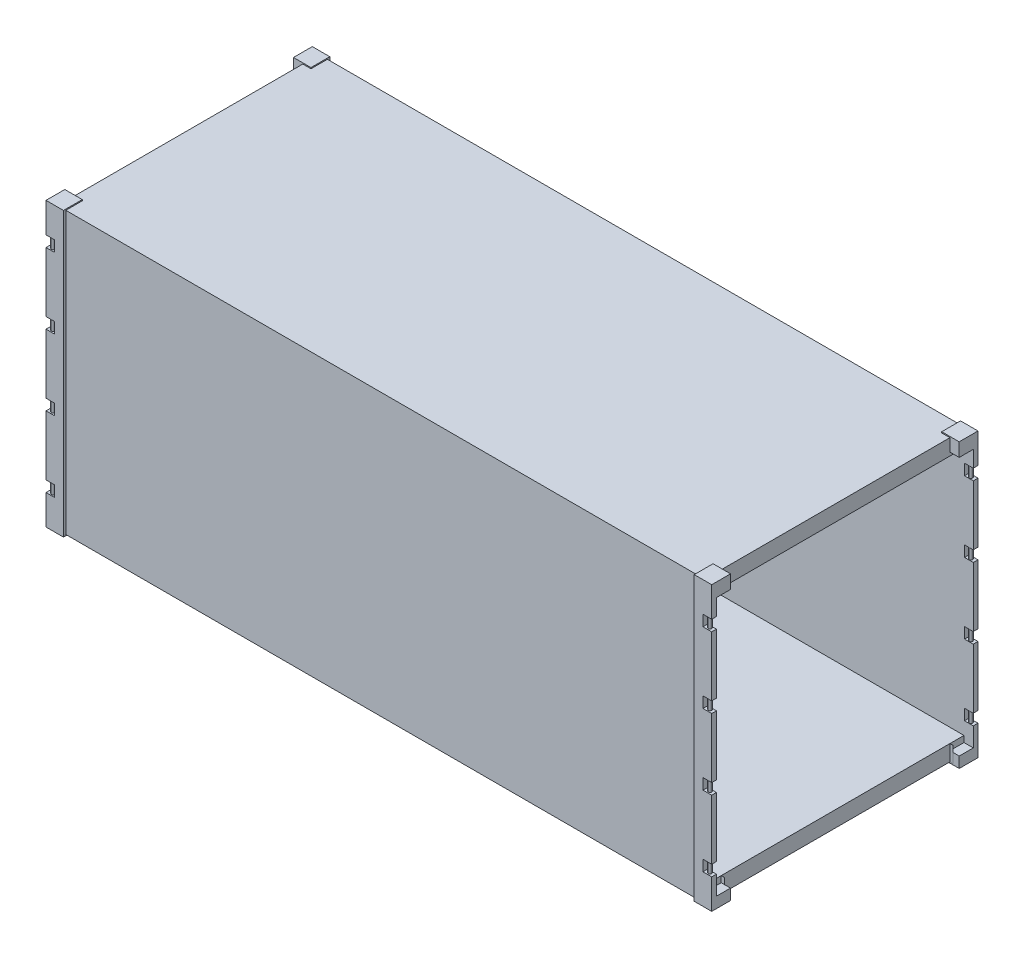
SolidWorks part; units mm, degrees
material "AISI 1015 Steel, Cold Drawn (SS)"
ref_plane "Front Plane" through (0, 0, 0) normal (0, 0, 1) x (1, 0, 0)
ref_plane "Top Plane" through (0, 0, 0) normal (0, 1, 0) x (1, 0, 0)
ref_plane "Right Plane" through (0, 0, 0) normal (1, 0, 0) x (0, 0, -1)
ref_plane "Plane1" through (0, 0, 2438) normal (0, 0, 1) x (1, 0, 0)
sketch "Sketch1" plane through (0, 0, 2438) normal (0, 0, 1) x (1, 0, 0)
  line L0 (3048, 10) -> (3048, 2591)
  line L1 (3048, 2591) -> (0, 2591)
  line L2 (0, 2591) -> (0, 10)
  line L3 (0, 10) -> (3048, 10)
  dimension "D1" = 3048
extrude "Boss-Extrude1" add sketch "Sketch1" against normal blind 1219.2
sketch "Sketch2" plane through (0, 2591, 0) normal (0, 1, 0) x (-1, 0, 0)
  line L0 (-160.02, 2438) -> (-3048, 2438)
  line L1 (-3048, 2438) -> (-3048, 2416.41)
  line L2 (-3048, 2416.41) -> (-160.02, 2416.41)
  line L3 (-160.02, 2416.41) -> (-160.02, 2438)
  line L4 (0, 1218.8) -> (0, 2438) construction
  line L5 (-3048, 2438) -> (0, 2438) construction
  line L6 (-3048, 1218.8) -> (-3048, 2438) construction
  dimension "D1" = 160.02
  dimension "D2" = 21.59
extrude "Cut-Extrude1" cut sketch "Sketch2" against normal through all
sketch "Sketch3" plane through (0, 10, 0) normal (0, -1, 0) x (1, 0, 0)
  line L0 (160, 2266) -> (0, 2266)
  line L1 (0, 2266) -> (0, 2438)
  line L2 (0, 2438) -> (160, 2438)
  line L3 (160, 2438) -> (160, 2266)
extrude "Boss-Extrude2" add sketch "Sketch3" along normal blind 10
ref_plane "Plane2" through (0, 10, 0) normal (0, -1, 0) x (1, 0, 0)
ref_plane "Plane3" through (0, 2435.5, 0) normal (0, 1, 0) x (-1, 0, 0)
sketch "Sketch11" plane through (0, 2435.5, 0) normal (0, 1, 0) x (-1, 0, 0)
  line L0 (-57.15, 2266) -> (-57.15, 1218.8)
  line L1 (-57.15, 1218.8) -> (0, 1218.8)
  line L2 (0, 1218.8) -> (0, 2266)
  line L3 (0, 2266) -> (-57.15, 2266)
  line L6 (-160.02, 2438) -> (0, 2438) construction
  line L7 (-3048, 1218.8) -> (0, 1218.8) construction
  line L8 (0, 1218.8) -> (0, 2438) construction
  line L9 (-3048, 1218.8) -> (-3048, 2416.41) construction
  dimension "D1" = 172
  dimension "D2" = 2990.85
extrude "Cut-Extrude3" cut sketch "Sketch11" against normal up to surface up to plane "Plane2"
ref_plane "Plane4" through (0, 0, 2389) normal (0, 0, 1) x (1, 0, 0)
ref_plane "Plane5" through (0, 0, 49) normal (0, 0, -1) x (-1, 0, 0)
ref_plane "Plane6" through (0, 155.5, 0) normal (0, -1, 0) x (1, 0, 0)
sketch "Sketch18" plane through (0, 155.5, 0) normal (0, -1, 0) x (1, 0, 0)
  line L0 (0, 2394.82) -> (0, 1218.8)
  line L1 (0, 1218.8) -> (3048, 1218.8)
  line L2 (3048, 1218.8) -> (3048, 2394.82)
  line L3 (3048, 2394.82) -> (0, 2394.82)
  line L9 (0, 1218.8) -> (0, 2438) construction
  line L10 (3048, 1218.8) -> (0, 1218.8) construction
  line L11 (3048, 1218.8) -> (3048, 2416.41) construction
  dimension "D1" = 1176.02
extrude "Cut-Extrude10" cut sketch "Sketch18" against normal blind 2387.6
ref_plane "Plane7" through (160, 0, 0) normal (-1, 0, 0) x (0, -1, 0)
sketch "Sketch20" plane through (0, 2591, 0) normal (0, 1, 0) x (-1, 0, 0)
  line L0 (0, 171.8) -> (0, 2265.8)
  line L1 (0, 2265.8) -> (-85.09, 2265.8)
  line L2 (-85.09, 2265.8) -> (-85.09, 171.8)
  line L3 (-85.09, 171.8) -> (0, 171.8)
  line L4 (-3048, 1218.8) -> (0, 1218.8) construction
  line L5 (0, 1218.8) -> (0, 2438) construction
  point P4 (-85.09, 1218.8)
  dimension "D1" = 85.09
  dimension "D2" = 2094
extrude "Cut-Extrude12" cut sketch "Sketch20" against normal through all
sketch "Sketch16" plane through (0, 155.5, 0) normal (0, 1, 0) x (-1, 0, 0)
  line L0 (0, 2394.82) -> (-85.09, 2394.82)
  line L1 (-85.09, 2394.82) -> (-85.09, 2266)
  line L2 (-85.09, 2266) -> (0, 2266)
  line L3 (0, 2266) -> (0, 2394.82)
  line L4 (-3048, 2394.82) -> (0, 2394.82) construction
  line L5 (0, 2266) -> (-57.15, 2266) construction
  line L8 (0, 2394.82) -> (0, 2266) construction
  line L9 (-85.09, 1218.8) -> (-85.09, 2265.8) construction
extrude "Cut-Extrude8" cut sketch "Sketch16" against normal blind 56.5
sketch "Sketch29" plane through (0, 0, 2438) normal (0, 0, 1) x (1, 0, 0)
  line L0 (0, 2317.125) -> (0, 2217.125)
  line L1 (0, 2217.125) -> (80, 2217.125)
  line L2 (80, 2217.125) -> (80, 2317.125)
  line L3 (80, 2317.125) -> (0, 2317.125)
extrude "Cut-Extrude19" cut sketch "Sketch29" against normal up to next
sketch "Sketch36" plane through (0, 10, 0) normal (0, -1, 0) x (1, 0, 0)
  line L0 (3048, 1218.8) -> (3048, 2314.81)
  line L1 (3048, 2314.81) -> (186.69, 2314.81)
  line L2 (186.69, 2314.81) -> (186.69, 1218.8)
  line L3 (186.69, 1218.8) -> (3048, 1218.8)
  line L5 (3048, 1218.8) -> (3048, 2416.41) construction
  line L8 (85.09, 1218.8) -> (85.09, 2266) construction
  line L9 (3048, 2416.41) -> (160.02, 2416.41) construction
  line L10 (85.09, 1218.8) -> (3048, 1218.8) construction
  dimension "D1" = 101.6
  dimension "D2" = 101.6
extrude "Cut-Extrude25" cut sketch "Sketch36" against normal blind 132.7988
ref_plane "Plane8" through (0, 0, 24.5) normal (0, 0, -1) x (-1, 0, 0)
ref_plane "Plane9" through (0, 0, 2413.5) normal (0, 0, -1) x (-1, 0, 0)
sketch "Sketch44" plane through (0, 0, 2413.5) normal (0, 0, -1) x (-1, 0, 0)
  line L0 (-55, 2217.125) -> (-40, 2217.125)
  line L1 (-40, 2217.125) -> (-40, 2317.125)
  line L2 (-40, 2317.125) -> (-55, 2317.125)
  line L3 (-55, 2317.125) -> (-55, 2217.125)
  line L4 (-40, 2217.125) -> (-40, 2317.125) construction
revolve "Revolve8" add sketch "Sketch44" angle 360 about L4 reverse direction yes
sketch "Sketch45" plane through (0, 2591, 0) normal (0, 1, 0) x (-1, 0, 0)
  line L0 (-3048, 1218.8) -> (-3048, 2416.41)
  line L1 (0, 2265.8) -> (-85.09, 2265.8) construction
  line L2 (-85.09, 1218.8) -> (-3048, 1218.8)
  line L3 (-160.02, 2416.41) -> (-160.02, 2438) construction
  line L4 (-3048, 2416.41) -> (-160.02, 2416.41) construction
  line L5 (-85.09, 1218.8) -> (-85.09, 2265.8)
  line L6 (-85.09, 2265.8) -> (-160.02, 2265.8)
  line L7 (-160.02, 2265.8) -> (-160.02, 2416.41)
  line L8 (-160.02, 2416.41) -> (-3048, 2416.41)
  line L9 (-85.09, 2265.8) -> (-85.09, 1218.8) construction
extrude "Cut-Extrude26" cut sketch "Sketch45" against normal blind 10
ref_plane "Plane10" through (3048, 0, 0) normal (1, 0, 0) x (0, 0, -1)
ref_plane "Plane11" through (0, 0, 1218.8) normal (0, 0, -1) x (-1, 0, 0)
pattern_linear "LPattern1" count 4 spacing 647.75 along (0, -1, 0) of "Cut-Extrude19", "Revolve8"
sketch "Sketch54" plane through (0, 2543.1, 0) normal (0, -1, 0) x (1, 0, 0)
  line L0 (3048, 2394.82) -> (0, 2394.82) construction
  line L1 (0, 2265.8) -> (85.09, 2265.8)
  line L2 (0, 2265.8) -> (0, 2394.82)
  line L3 (0, 2394.82) -> (85.09, 2394.82)
  line L4 (85.09, 2265.8) -> (85.09, 2394.82)
  line L5 (85.09, 1218.8) -> (85.09, 2265.8) construction
extrude "Boss-Extrude4" add sketch "Sketch54" along normal blind 76.2
sketch "Sketch53" plane through (0, 0, 2394.82) normal (0, 0, -1) x (-1, 0, 0)
  line L1 (-85.09, 2543.1) -> (-237.49, 2543.1)
  line L2 (-85.09, 2543.1) -> (-85.09, 2435.404)
  line L3 (-85.09, 2435.404) -> (-237.49, 2435.404)
  line L4 (-237.49, 2543.1) -> (-237.49, 2435.404)
  line L5 (-3048, 155.5) -> (-85.09, 155.5) construction
  dimension "D1" = 152.4
  dimension "D2" = 2279.904
extrude "Boss-Extrude3" add sketch "Sketch53" along normal up to surface (1176.02 mm away) up to plane "Plane11"
mirror "Mirror2" about plane through (0, 0, 1218.8) normal (0, 0, -1) of "Boss-Extrude4", "Cut-Extrude8", "LPattern1", "Revolve8", "Cut-Extrude19", "Cut-Extrude26", "Cut-Extrude25", "Cut-Extrude12", "Cut-Extrude10", "Cut-Extrude3", "Boss-Extrude2", "Cut-Extrude1", "Boss-Extrude1", "Boss-Extrude3"
mirror "Mirror1" about plane through (3048, 0, 0) normal (1, 0, 0) of "Cut-Extrude26", "Revolve8", "Cut-Extrude25", "Cut-Extrude19", "Cut-Extrude10", "Cut-Extrude3", "Boss-Extrude2", "Cut-Extrude1", "Boss-Extrude1", "Cut-Extrude12", "Mirror2", "LPattern1", "Cut-Extrude8"
